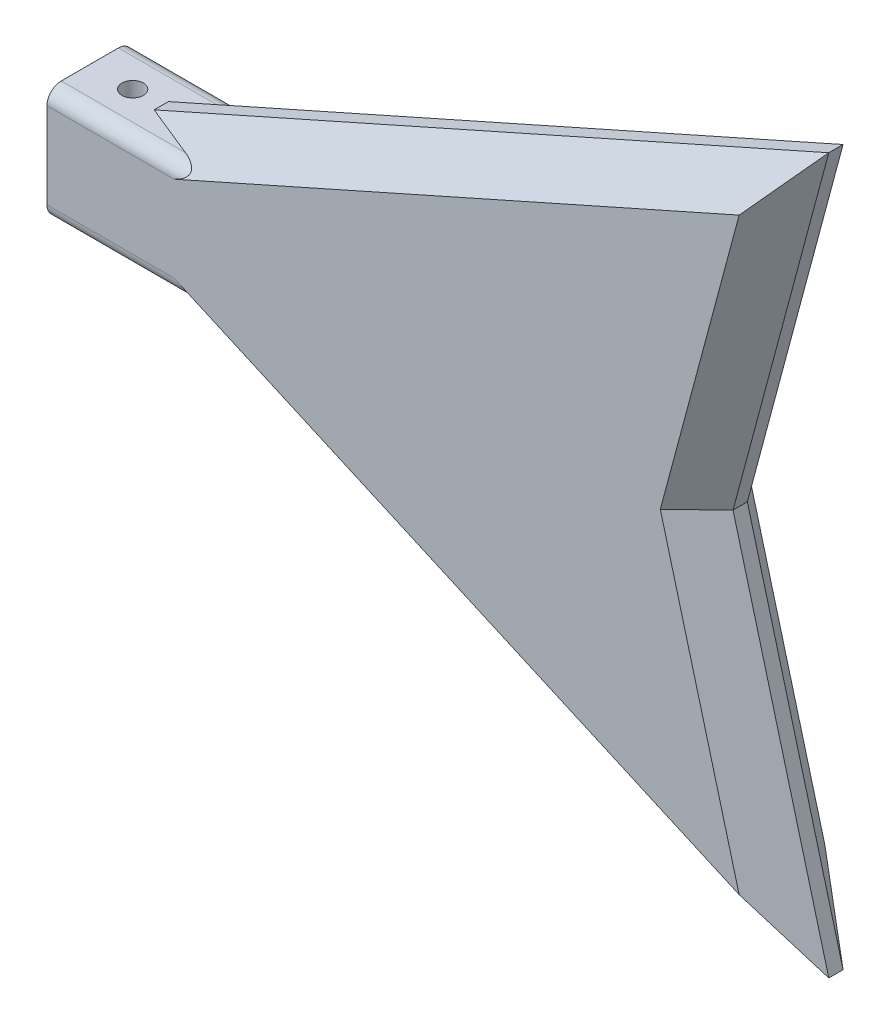
SolidWorks part; units mm, degrees
ref_plane "Ön Düzlem" through (0, 0, 0) normal (0, 0, 1) x (1, 0, 0)
ref_plane "Üst Düzlem" through (0, 0, 0) normal (0, 1, 0) x (1, 0, 0)
ref_plane "Sağ Düzlem" through (0, 0, 0) normal (1, 0, 0) x (0, 0, -1)
sketch "Sketch1" plane through (0, 0, 0) normal (0, 0, 1) x (1, 0, 0)
  line L4 (10, -8) -> (104.3975, -50)
  line L5 (104.3975, -50) -> (91, 0)
  line L7 (10, -8) -> (0, -8)
  line L8 (0, -8) -> (0, 8)
  line L10 (91, 0) -> (0, 0) construction
  line L11 (10, 8) -> (0, 8)
  line L12 (10, 8) -> (104.3975, 50)
  line L13 (104.3975, 50) -> (91, 0)
  dimension "D1" = 91
  dimension "D2" = 8
  dimension "D3" = 50
  dimension "D4" = 105
  dimension "D5" = 10
extrude "Boss-Extrude8" add sketch "Sketch1" along normal mid plane 12
sketch "Sketch7" plane through (0, 0, 0) normal (-1, 0, 0) x (0, 0, 1)
  circle A0 centre (0, 0) radius 5
  dimension "D1" = 10
extrude "Cut-Extrude3" cut sketch "Sketch7" against normal blind 14
sketch "Sketch8" plane through (0, 8, 0) normal (0, 1, 0) x (1, 0, 0)
  line L0 (0, -6) -> (0, 6) construction
  circle A0 centre (6, 0) radius 1.5
  dimension "D1" = 3
  dimension "D2" = 6
extrude "Cut-Extrude4" cut sketch "Sketch8" against normal through all
chamfer "Chamfer3" distance 5 angle 45 8 edges at (57.1987, -29, 6) (97.6987, -25, 6) (97.6987, 25, 6) (57.1987, 29, 6) (57.1987, -29, -6) (97.6987, -25, -6) (97.6987, 25, -6) (57.1987, 29, -6)
fillet "Fillet4" radius 2 4 edges at (11.15, -8, 6) (11.15, -8, -6) (11.15, 8, -6) (11.15, 8, 6)
